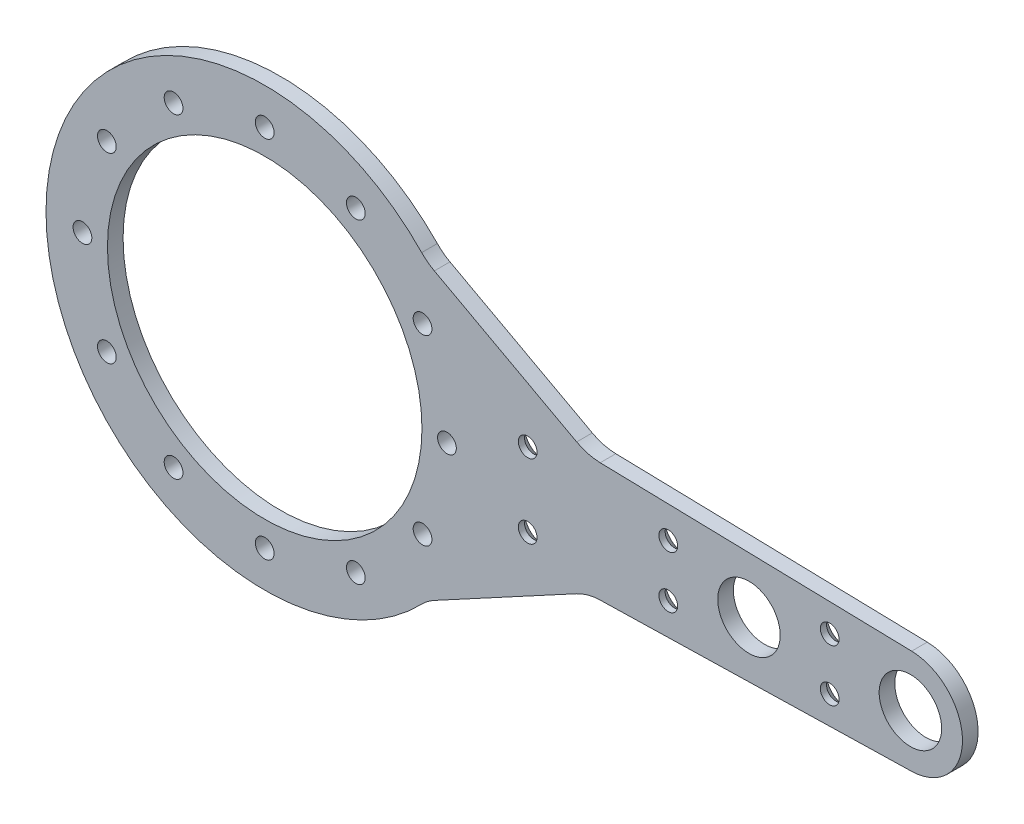
SolidWorks part; units mm, degrees
material "Hexcel AS4C (3000 Filaments)"
ref_plane "Front Plane" through (0, 0, 0) normal (0, 0, 1) x (1, 0, 0)
ref_plane "Top Plane" through (0, 0, 0) normal (0, 1, 0) x (1, 0, 0)
ref_plane "Right Plane" through (0, 0, 0) normal (1, 0, 0) x (0, 0, -1)
sketch "Sketch1" plane through (0, 0, 0) normal (0, 0, 1) x (1, 0, 0)
  line L0 (20.1246, 6) -> (62.1192, 4.9986)
  line L1 (20.1246, -6) -> (62.1192, -4.9986)
  line L2 (20.1246, 6) -> (20.1246, -6) construction
  circle A0 centre (0, 0) radius 15.1
  arc A1 (20.1246, 6) -> (20.1246, -6) centre (0, 0) ccw
  circle A2 centre (46.5, 0) radius 3
  circle A3 centre (62, 0) radius 3
  arc A4 (62.1192, -4.9986) -> (62.1192, 4.9986) centre (62, 0) ccw
  circle A5 centre (0, 0) radius 17.5 construction
  dimension "D1" = 21
  dimension "D4" = 6
  dimension "D3" = 30.2
  dimension "D5" = 62
  dimension "D7" = 5
  dimension "D8" = 35
  dimension "D2" = 15.5
  dimension "D6" = 12
extrude "Boss-Extrude1" add sketch "Sketch1" along normal blind 1.5
hole_wizard "M1.6 Clearance Hole2" positions "Sketch5" profile "Sketch4" hole size "M1.6" standard "DIN"
sketch "Sketch5" plane through (0, 0, 1.5) normal (0, 0, 1) x (1, 0, 0)
  circle A0 centre (0, 0) radius 17.5
  point P0 (0, 17.5)
  dimension "D1" = 35
sketch "Sketch4" plane through (0, 17.5, 1.5) normal (1, 0, 0) x (0, -1, 0)
  line L0 (0, 0) -> (0, 11.5)
  line L1 (0, 11.5) -> (0.9, 11.5)
  line L2 (0.9, 11.5) -> (0.9, 0)
  line L5 (0.9, 0) -> (0, 0)
  line L10 (0, 11.5) -> (-0.9, 11.5) construction
  line L11 (0, -6.35) -> (0, 107.95) construction
  dimension "Hole Dia." = 1.8
  dimension "Hole Depth" = 11.5
  dimension "Drill Angle" = 180
pattern_circular "CirPattern1" count 12 over 360 about axis through (0, 0, 1.5) along (0, 0, -1) of "M1.6 Clearance Hole2"
hole_wizard "M1.6 Clearance Hole1" positions "Sketch7" profile "Sketch6" hole size "M1.6" standard "DIN"
sketch "Sketch7" plane through (0, 0, 1.5) normal (0, 0, 1) x (1, 0, 0)
  line L6 (0, 0) -> (62, 0) construction
  line L8 (46.5, 0) -> (46.5, -10.138) construction
  line L10 (62, 0) -> (62, -7.973) construction
  line L12 (54.25, -2.5) -> (38.75, -2.5)
  line L13 (54.25, -2.5) -> (54.25, 2.5)
  line L14 (54.25, 2.5) -> (38.75, 2.5)
  line L15 (38.75, -2.5) -> (38.75, 2.5)
  line L16 (54.25, -2.5) -> (38.75, 2.5) construction
  line L17 (54.25, 2.5) -> (38.75, -2.5) construction
  point P283 (38.75, 2.5)
  point P285 (54.25, -2.5)
  point P407 (38.75, -2.5)
  point P409 (54.25, 2.5)
  dimension "D1" = 5
  dimension "D2" = 15.5
sketch "Sketch6" plane through (38.75, 2.5, 1.5) normal (1, 0, 0) x (0, -1, 0)
  line L0 (0, 0) -> (0, 11.5)
  line L1 (0, 11.5) -> (0.9, 11.5)
  line L2 (0.9, 11.5) -> (0.9, 0)
  line L5 (0.9, 0) -> (0, 0)
  line L10 (0, 11.5) -> (-0.9, 11.5) construction
  line L11 (0, -6.35) -> (0, 107.95) construction
  dimension "Hole Dia." = 1.8
  dimension "Hole Depth" = 11.5
  dimension "Drill Angle" = 180
chamfer "Chamfer2" distance 7 angle 45 2 edges at (20.1246, -6, 0.75) (20.1246, 6, 0.75) first distance on face at (-0.4377, 0, 0.75)
fillet "Fillet4" radius 5 4 edges at (31.0122, -5.7404, 0.75) (15.574, -14.0872, 0.75) (15.574, 14.0872, 0.75) (31.0122, 5.7404, 0.75)
chamfer "Chamfer3" distance 0.9 angle 45 4 edges at (55.15, 2.5, 0) (39.65, -2.5, 0) (55.15, -2.5, 0) (39.65, 2.5, 0)
sketch "Esquisse1" plane through (0, 0, 0) normal (0, 0, -1) x (-1, 0, 0)
  line L0 (0, 0) -> (-25.2518, 3.5489) construction
  line L1 (0, 0) -> (-25.2518, -3.5489) construction
  line L2 (0, 0) -> (-25.5, 0) construction
  circle A0 centre (0, 0) radius 21.5 construction
  circle A1 centre (0, 0) radius 25.5 construction
  circle A2 centre (-25.2518, 3.5489) radius 0.9
  circle A3 centre (-25.2518, -3.5489) radius 0.9
  dimension "D1" = 43
  dimension "D2" = 4
  dimension "D5" = 1.8
  dimension "D6" = 1.8
  dimension "D3" = 8
  dimension "D4" = 8
extrude "Enlèv. mat.-Extru.1" cut sketch "Esquisse1" against normal through all
chamfer "Chanfrein1" distance 0.9 angle 45 2 edges at (24.3518, -3.5489, 0) (24.3518, 3.5489, 0)
